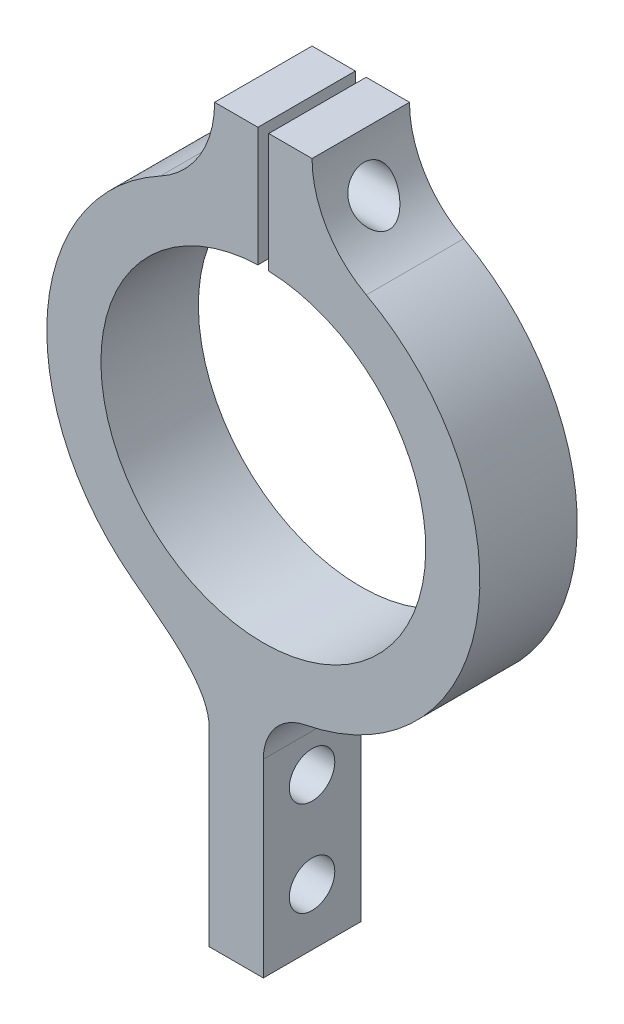
SolidWorks part; units mm, degrees
ref_plane "Front Plane" through (0, 0, 0) normal (0, 0, 1) x (1, 0, 0)
ref_plane "Top Plane" through (0, 0, 0) normal (0, 1, 0) x (1, 0, 0)
ref_plane "Right Plane" through (0, 0, 0) normal (1, 0, 0) x (0, 0, -1)
sketch "Sketch1" plane through (0, 0, 0) normal (0, 0, 1) x (1, 0, 0)
  line L0 (0, 0) -> (0, 40) construction
  line L1 (0, -48.6004) -> (0, -83.6004)
  line L2 (0, -83.6004) -> (-10, -83.6004)
  line L3 (-10, -83.6004) -> (-10, -48.6004)
  line L4 (30, 0) -> (40, 0) construction
  line L6 (0, 40) -> (0, 52) construction
  line L7 (0, 52) -> (1, 52) construction
  line L8 (1, 52) -> (1, 29.9833)
  line L9 (1, 52) -> (9, 52)
  line L11 (0, 52) -> (-1, 52) construction
  line L12 (-1, 52) -> (-1, 29.9833)
  line L13 (-1, 52) -> (-9, 52)
  arc A0 (-1, 29.9833) -> (1, 29.9833) centre (0, 0) ccw
  arc A1 (0, -48.6004) -> (7.6931, -39.2532) centre (9.525, -48.6004) cw
  arc A2 (0, 40) -> (-1, 39.9875) centre (0, 0) ccw construction
  arc A3 (9, 52) -> (19.0232, 35.1869) centre (28.1129, 52) ccw
  arc A4 (-19.0232, 35.1869) -> (-26.5352, -29.9313) centre (0, 0) ccw
  arc A6 (-19.0232, 35.1869) -> (-9, 52) centre (-28.1129, 52) ccw
  arc A8 (7.6931, -39.2532) -> (19.0232, 35.1869) centre (0, 0) ccw
  spline S0 degree 3 poles (-26.5352, -29.9313) (-20.9482, -34.8844) (-10, -40.904) (-10, -48.6004) knots 0 0 0 0 1 1 1 1
  point P27 (0, -40)
  dimension "D1" = 60
  dimension "D3" = 35
  dimension "D4" = 10
  dimension "D2" = 10
  dimension "D11" = 9.525
  dimension "D6" = 12
  dimension "D7" = 1
  dimension "D8" = 8
  dimension "D9" = 1
  dimension "D10" = 8
extrude "Boss-Extrude1" add sketch "Sketch1" along normal blind 18
sketch "Sketch7" plane through (1, 0, 0) normal (-1, 0, 0) x (0, 0, 1)
  line L3 (9, 43) -> (9, 52) construction
  line L4 (18, 52) -> (0, 52) construction
  line L5 (9, 43) -> (0, 43) construction
  line L6 (0, 52) -> (0, 35.1869) construction
  circle A0 centre (9, 43) radius 4
  point P8 (0, 41.49)
  dimension "D1" = 8
sketch "Sketch12" plane through (0, 0, 0) normal (1, 0, 0) x (0, 0, -1)
  line L0 (-9, -48.6004) -> (-9, -55.6004) construction
  line L1 (-9, -62.6004) -> (-9, -73.1004) construction
  line L2 (-18, -48.6004) -> (0, -48.6004) construction
  line L3 (-9, -73.1004) -> (-9, -83.6004) construction
  line L4 (-18, -83.6004) -> (0, -83.6004) construction
  circle A0 centre (-9, -55.6004) radius 4
  circle A1 centre (-9, -55.6004) radius 7 construction
  circle A2 centre (-9, -73.1004) radius 4
  circle A3 centre (-9, -73.1004) radius 7 construction
  dimension "D1" = 8
  dimension "D2" = 14
  dimension "D3" = 14
  dimension "D4" = 8
hole_wizard "M8 Clearance Hole1" positions "Sketch13" profile "Sketch14" hole size "M8" standard "ANSI Metric" end condition through all
sketch "Sketch13" plane through (1, 0, 0) normal (-1, 0, 0) x (0, 0, 1)
  point P0 (9, 43)
sketch "Sketch14" plane through (1, 43, 9) normal (0, 1, 0) x (0, 0, 1)
  line L0 (0, 0) -> (0, 39)
  line L1 (0, 39) -> (4.2, 39)
  line L2 (4.2, 39) -> (4.2, 0)
  line L5 (4.2, 0) -> (0, 0)
  line L11 (0, -6.35) -> (0, 107.95) construction
  dimension "Thru Hole Dia." = 8.4
  dimension "Thru Hole Depth" = 39
hole_wizard "M8 Clearance Hole2" positions "Sketch15" profile "Sketch16" hole size "M8" standard "ANSI Metric" end condition through all
sketch "Sketch15" plane through (1, 0, 0) normal (-1, 0, 0) x (0, 0, 1)
  point P0 (9, 43)
sketch "Sketch16" plane through (1, 43, 9) normal (0, 1, 0) x (0, 0, -1)
  line L0 (0, 0) -> (0, 41)
  line L1 (0, 41) -> (4.2, 41)
  line L2 (4.2, 41) -> (4.2, 0)
  line L5 (4.2, 0) -> (0, 0)
  line L11 (0, -6.35) -> (0, 107.95) construction
  dimension "Thru Hole Dia." = 8.4
  dimension "Thru Hole Depth" = 41
sketch "Sketch17" plane through (0, 0, 18) normal (0, 0, 1) x (1, 0, 0)
  line L0 (-9, 52) -> (-9, 28.6182)
  line L1 (9, 52) -> (9, 28.6182)
  arc A0 (-1, 29.9833) -> (1, 29.9833) centre (0, 0) ccw construction
hole_wizard "M8 Clearance Hole3" positions "Sketch18" profile "Sketch19" hole size "M8" standard "ANSI Metric" end condition through all
sketch "Sketch18" plane through (0, 0, 0) normal (1, 0, 0) x (0, 0, -1)
  point P0 (-9, -55.6004)
  point P3 (-9, -73.1004)
sketch "Sketch19" plane through (0, -55.6004, 9) normal (0, 1, 0) x (0, 0, -1)
  line L0 (0, 0) -> (0, 40)
  line L1 (0, 40) -> (4.2, 40)
  line L2 (4.2, 40) -> (4.2, 0)
  line L5 (4.2, 0) -> (0, 0)
  line L11 (0, -6.35) -> (0, 107.95) construction
  dimension "Thru Hole Dia." = 8.4
  dimension "Thru Hole Depth" = 40
ref_plane "Plane1" through (-9, 0, 0) normal (-1, 0, 0) x (0, 0, 1)
sketch "Sketch26" plane through (-9, 0, 0) normal (-1, 0, 0) x (0, 0, 1)
  line L0 (18, 52) -> (18, 28.6182) construction
  line L1 (0, 52) -> (18, 52)
  line L2 (0, 52) -> (0, 35.7571)
  line L3 (0, 35.7571) -> (18, 35.7571)
  line L4 (18, 52) -> (18, 35.7571)
